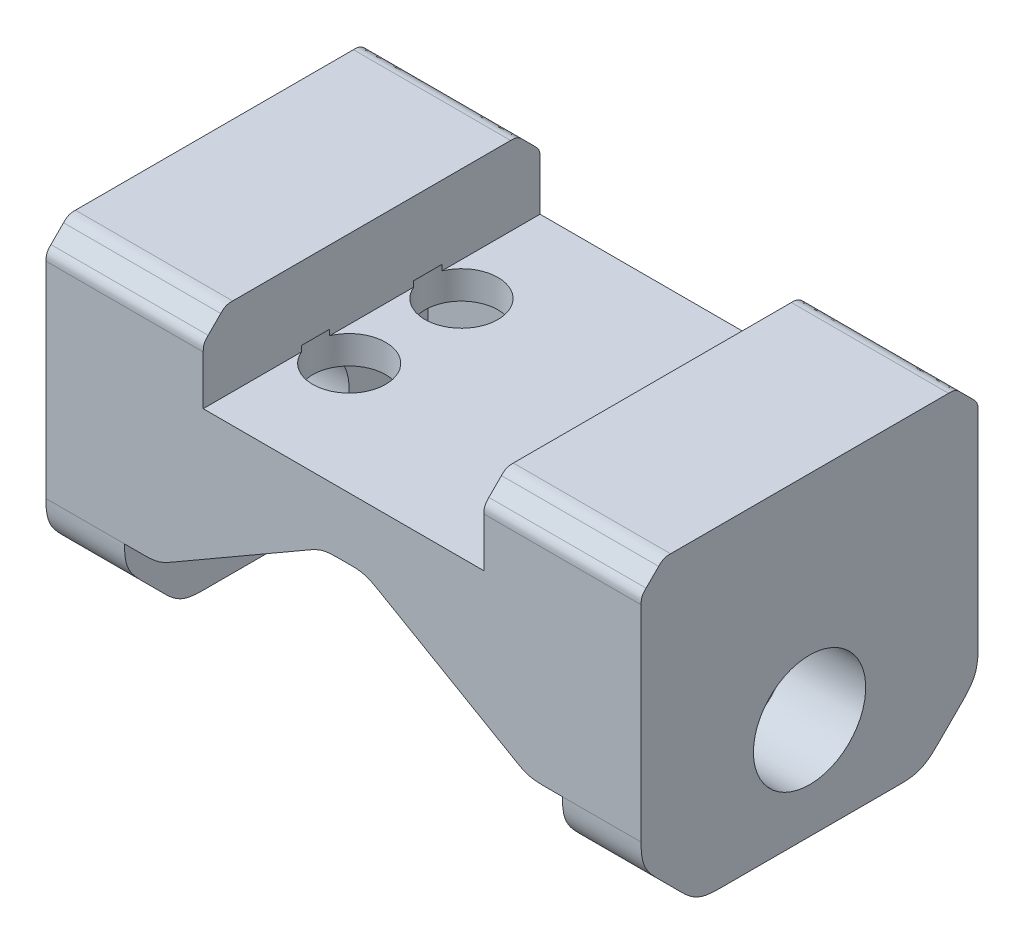
SolidWorks part; units mm, degrees
ref_plane "Front Plane" through (0, 0, 0) normal (0, 0, 1) x (1, 0, 0)
ref_plane "Top Plane" through (0, 0, 0) normal (0, 1, 0) x (1, 0, 0)
ref_plane "Right Plane" through (0, 0, 0) normal (1, 0, 0) x (0, 0, -1)
sketch "Sketch1" plane through (0, 0, 0) normal (0, 1, 0) x (1, 0, 0)
  line L9 (-26.5, 15) -> (26.5, 15)
  line L15 (-26.5, 15) -> (-26.5, -15)
  line L16 (-26.5, -15) -> (26.5, -15)
  line L17 (26.5, 15) -> (26.5, -15)
  line L18 (-26.5, 15) -> (26.5, -15) construction
  line L19 (-26.5, -15) -> (26.5, 15) construction
  point P0 (0, 0)
  dimension "D1" = 53
  dimension "D2" = 30
extrude "Boss-Extrude1" add sketch "Sketch1" along normal blind 2.5
sketch "Sketch2" plane through (0, 2.5, 0) normal (0, 1, 0) x (1, 0, 0)
  line L0 (-26.5, -15) -> (26.5, -15) construction
  line L1 (-26.5, 15) -> (-12.5, 15)
  line L2 (-26.5, 15) -> (-26.5, -15)
  line L3 (-26.5, -15) -> (-12.5, -15)
  line L4 (-12.5, 15) -> (-12.5, -15)
  line L5 (0, 15) -> (0, -15) construction
  line L6 (26.5, 15) -> (-26.5, 15) construction
  line L7 (26.5, -15) -> (12.5, -15)
  line L8 (12.5, 15) -> (12.5, -15)
  line L9 (26.5, 15) -> (12.5, 15)
  line L10 (26.5, 15) -> (26.5, -15)
  dimension "D1" = 25
extrude "Boss-Extrude2" add sketch "Sketch2" along normal blind 7
sketch "Sketch3" plane through (-26.5, 0, 0) normal (-1, 0, 0) x (0, 0, 1)
  line L0 (-15, 2.5) -> (15, 2.5) construction
  line L1 (-15, 0) -> (-15, -18.5)
  line L4 (-15, -18.5) -> (15, -18.5)
  line L5 (0, -18.5) -> (0, 0) construction
  line L8 (15, 0) -> (15, -18.5)
  line L9 (-15, 0) -> (15, 0)
  circle A0 centre (0, -9.5) radius 5
  point P4 (-15, -15.5)
  point P13 (-14.7159, -15.5)
  point P16 (0, 0)
  dimension "D1" = 10
  dimension "D2" = 12
  dimension "D4" = 4
extrude "Boss-Extrude3" add sketch "Sketch3" against normal blind 7
chamfer "Chamfer1" distance 5 angle 45 2 edges at (-23, -18.5, 15) (-23, -18.5, -15)
fillet "Fillet1" radius 5 4 edges at (-23, -13.5, 15) (-23, -18.5, 10) (-23, -18.5, -10) (-23, -13.5, -15) curvature continuous yes
mirror "Mirror1" about plane through (0, 0, 0) normal (1, 0, 0) of "Fillet1", "Chamfer1", "Boss-Extrude3"
chamfer "Chamfer2" distance 2 angle 45 4 edges at (-19.5, 9.5, -15) (-19.5, 9.5, 15) (19.5, 9.5, 15) (19.5, 9.5, -15)
fillet "Fillet2" radius 1.5 8 edges at (19.5, 7.5, -15) (19.5, 9.5, -13) (19.5, 7.5, 15) (19.5, 9.5, 13) (-19.5, 7.5, 15) (-19.5, 9.5, 13) (-19.5, 7.5, -15) (-19.5, 9.5, -13) curvature continuous yes
sketch "Sketch4" plane through (0, 0, -15) normal (0, 0, -1) x (-1, 0, 0)
  line L1 (-19.5, 0) -> (19.5, 0) construction
  line L2 (0, 0) -> (-19.5, 0)
  line L3 (-19.5, 0) -> (-19.5, -11.4289)
  line L4 (-19.5, -11.4289) -> (-16.5, -11.4289)
  line L5 (-16.5, -11.4289) -> (-1.9007, -3)
  line L7 (0, 15.455) -> (0, -15.455) construction
  line L8 (16.5, -11.4289) -> (1.9007, -3)
  line L9 (19.5, -11.4289) -> (16.5, -11.4289)
  line L10 (19.5, 0) -> (19.5, -11.4289)
  line L11 (0, 0) -> (19.5, 0)
  line L12 (-1.9007, -3) -> (1.9007, -3)
  dimension "D1" = 3
  dimension "D2" = 3
  dimension "D3" = 30
extrude "Boss-Extrude4" add sketch "Sketch4" against normal blind 3
fillet "Fillet3" radius 5 4 edges at (-1.9007, -3, -13.5) (-16.5, -11.4289, -13.5) (1.9007, -3, -13.5) (16.5, -11.4289, -13.5) curvature continuous yes
mirror "Mirror2" about plane through (0, 0, 0) normal (0, 0, 1) of "Fillet3", "Boss-Extrude4"
hole_wizard "CBORE for M3 SHCS1" positions "Sketch5" profile "Sketch6" counterbore size "M3" standard "ANSI Metric"
sketch "Sketch5" plane through (0, 0, 0) normal (0, -1, 0) x (-1, 0, 0)
  point P1 (-9.5, 5)
  point P4 (9.5, 5)
  point P7 (9.5, -5)
  point P10 (-9.5, -5)
sketch "Sketch6" plane through (9.5, 0, -5) normal (1, 0, 0) x (0, 0, -1)
  line L0 (0, 0) -> (0, 13.4215)
  line L1 (0, 13.4215) -> (1.7, 12.4)
  line L2 (1.7, 12.4) -> (1.7, 3)
  line L3 (1.7, 3) -> (3.25, 3)
  line L4 (3.25, 3) -> (3.25, 0)
  line L5 (3.25, 0) -> (0, 0)
  line L10 (0, 13.4215) -> (-1.7, 12.4) construction
  line L11 (0, -6.35) -> (0, 107.95) construction
  dimension "Hole Dia." = 3.4
  dimension "Hole Depth" = 12.4
  dimension "C'Bore Dia." = 6.5
  dimension "C'Bore Depth" = 3
  dimension "Drill Angle" = 118
